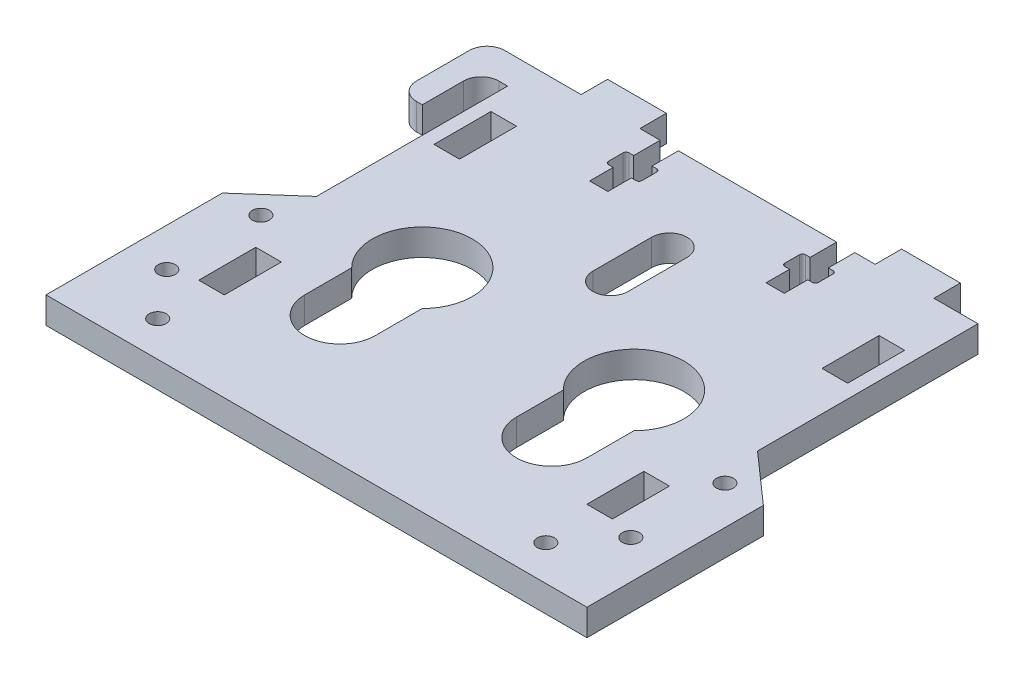
SolidWorks part; units mm, degrees
ref_plane "Front Plane" through (0, 0, 0) normal (0, 0, 1) x (1, 0, 0)
ref_plane "Top Plane" through (0, 0, 0) normal (0, 1, 0) x (1, 0, 0)
ref_plane "Right Plane" through (0, 0, 0) normal (1, 0, 0) x (0, 0, -1)
sketch "Sketch1" plane through (0, 0, 0) normal (0, 1, 0) x (1, 0, 0)
  line L1 (-37.5, 37.5) -> (37.5, 37.5)
  line L2 (-37.5, 37.5) -> (-37.5, -37.5)
  line L3 (-37.5, -37.5) -> (37.5, -37.5)
  line L4 (37.5, 37.5) -> (37.5, -37.5)
  line L5 (-37.5, 37.5) -> (37.5, -37.5) construction
  line L6 (-37.5, -37.5) -> (37.5, 37.5) construction
  point P0 (0, 0)
  dimension "D1" = 75
  dimension "D2" = 75
extrude "MainShape" add sketch "Sketch1" along normal blind 4.5
sketch "Sketch2" plane through (0, 4.5, 0) normal (0, 1, 0) x (1, 0, 0)
  line L0 (0, -37.5) -> (0, 37.5) construction
  line L1 (-37.5, -37.5) -> (37.5, -37.5) construction
  line L2 (37.5, 37.5) -> (-37.5, 37.5) construction
  line L4 (-5, 42) -> (5, 42)
  line L5 (-5, 42) -> (-5, 33)
  line L6 (-5, 33) -> (5, 33)
  line L7 (5, 42) -> (5, 33)
  line L8 (-5, 42) -> (5, 33) construction
  line L9 (-5, 33) -> (5, 42) construction
  dimension "D1" = 10
  dimension "D2" = 4.5
extrude "Tab1" [suppressed] add sketch "Sketch2" against normal through all
sketch "Sketch4" [suppressed] plane through (0, 4.5, 0) normal (0, 1, 0) x (1, 0, 0)
  line L0 (0, 42) -> (0, -37.5) construction
  line L1 (5, 42) -> (-5, 42) construction
  line L2 (-47.5, -37.5) -> (47.5, -37.5) construction
  line L3 (-40, 37.5) -> (-40, 27) construction
  line L4 (-5, 37.5) -> (-47.5, 37.5) construction
  line L5 (-38.25, 27) -> (-41.75, 27) construction
  line L6 (-41.75, 27) -> (-41.75, 37.5) construction
  line L7 (-38.25, 27) -> (-41.75, 27)
  line L8 (-41.75, 27) -> (-41.75, 29.5)
  line L9 (-41.75, 29.5) -> (-42.75, 29.5)
  line L10 (-43, 29.75) -> (-43, 33.45)
  line L11 (-42.75, 33.7) -> (-41.75, 33.7)
  line L12 (-41.75, 33.7) -> (-41.75, 37.5)
  line L13 (-41.75, 37.5) -> (-38.25, 37.5)
  line L14 (-38.25, 27) -> (-38.25, 37.5) construction
  line L15 (-38.25, 33.7) -> (-38.25, 37.5)
  line L16 (-37.25, 33.7) -> (-38.25, 33.7)
  line L17 (-37, 29.75) -> (-37, 33.45)
  line L18 (-38.25, 29.5) -> (-37.25, 29.5)
  line L19 (-38.25, 27) -> (-38.25, 29.5)
  line L20 (38.25, 27) -> (38.25, 37.5) construction
  line L21 (41.75, 27) -> (41.75, 37.5) construction
  line L22 (38.25, 27) -> (41.75, 27) construction
  line L23 (40, 37.5) -> (40, 27) construction
  line L24 (38.25, 27) -> (38.25, 29.5)
  line L25 (38.25, 29.5) -> (37.25, 29.5)
  line L26 (37, 29.75) -> (37, 33.45)
  line L27 (37.25, 33.7) -> (38.25, 33.7)
  line L28 (38.25, 33.7) -> (38.25, 37.5)
  line L29 (41.75, 37.5) -> (38.25, 37.5)
  line L30 (41.75, 33.7) -> (41.75, 37.5)
  line L31 (42.75, 33.7) -> (41.75, 33.7)
  line L32 (43, 29.75) -> (43, 33.45)
  line L33 (41.75, 29.5) -> (42.75, 29.5)
  line L34 (41.75, 27) -> (41.75, 29.5)
  line L35 (38.25, 27) -> (41.75, 27)
  arc A0 (-42.75, 29.5) -> (-43, 29.75) centre (-42.75, 29.75) cw
  arc A1 (-37, 29.75) -> (-37.25, 29.5) centre (-37.25, 29.75) cw
  arc A2 (-37.25, 33.7) -> (-37, 33.45) centre (-37.25, 33.45) cw
  arc A3 (-43, 33.45) -> (-42.75, 33.7) centre (-42.75, 33.45) cw
  arc A4 (43, 33.45) -> (42.75, 33.7) centre (42.75, 33.45) ccw
  arc A5 (37.25, 33.7) -> (37, 33.45) centre (37.25, 33.45) ccw
  arc A6 (37, 29.75) -> (37.25, 29.5) centre (37.25, 29.75) ccw
  arc A7 (42.75, 29.5) -> (43, 29.75) centre (42.75, 29.75) ccw
  point P24 (-43, 29.5)
  point P27 (-37, 29.5)
  point P30 (-37, 33.7)
  point P33 (-43, 33.7)
  point P56 (43, 33.7)
  point P57 (37, 33.7)
  point P58 (37, 29.5)
  point P59 (43, 29.5)
  dimension "D7" = 0.5
  dimension "D1" = 11
  dimension "D2" = 1.55
  dimension "D3" = 3.5
  dimension "D4" = 2.85
  dimension "D5" = 8
  dimension "D6" = 40
extrude "Cut-Extrude2" [suppressed] cut sketch "Sketch4" against normal through all
sketch "Sketch5" plane through (0, 4.5, 0) normal (0, 1, 0) x (1, 0, 0)
  line L0 (0, -37.5) -> (0, 37.5) construction
  line L1 (-37.5, -37.5) -> (37.5, -37.5) construction
  line L3 (33, 37.5) -> (33, -37.5) construction
  line L4 (37.5, 37.5) -> (-37.5, 37.5) construction
  line L5 (-33, 37.5) -> (-33, -37.5) construction
  line L6 (30.825, 27.35) -> (35.175, 27.35)
  line L7 (30.825, 27.35) -> (30.825, 17.65)
  line L8 (30.825, 17.65) -> (35.175, 17.65)
  line L9 (35.175, 27.35) -> (35.175, 17.65)
  line L10 (30.825, 27.35) -> (35.175, 17.65) construction
  line L11 (30.825, 17.65) -> (35.175, 27.35) construction
  line L12 (-30.825, 17.65) -> (-35.175, 27.35) construction
  line L13 (-30.825, 27.35) -> (-35.175, 17.65) construction
  line L14 (-35.175, 27.35) -> (-35.175, 17.65)
  line L15 (-30.825, 17.65) -> (-35.175, 17.65)
  line L16 (-30.825, 27.35) -> (-30.825, 17.65)
  line L17 (-30.825, 27.35) -> (-35.175, 27.35)
  line L18 (-37.5, 2.5) -> (37.5, 2.5) construction
  line L19 (-37.5, 37.5) -> (-37.5, -37.5) construction
  line L20 (37.5, -37.5) -> (37.5, 37.5) construction
  line L21 (-30.825, -22.35) -> (-35.175, -12.65) construction
  line L22 (-30.825, -12.65) -> (-35.175, -22.35) construction
  line L23 (30.825, -12.65) -> (35.175, -22.35) construction
  line L24 (30.825, -22.35) -> (35.175, -12.65) construction
  line L25 (-30.825, -22.35) -> (-35.175, -22.35)
  line L26 (-30.825, -22.35) -> (-30.825, -12.65)
  line L27 (-30.825, -12.65) -> (-35.175, -12.65)
  line L28 (-35.175, -22.35) -> (-35.175, -12.65)
  line L29 (35.175, -22.35) -> (35.175, -12.65)
  line L30 (30.825, -12.65) -> (35.175, -12.65)
  line L31 (30.825, -22.35) -> (30.825, -12.65)
  line L32 (30.825, -22.35) -> (35.175, -22.35)
  line L33 (-30.825, 27.35) -> (-35.175, 17.65) construction
  line L34 (-37.5, 37.5) -> (37.5, 37.5) construction
  line L35 (37.5, 37.5) -> (-37.5, 37.5) construction
  point P10 (33, 22.5)
  point P21 (-33, 22.5)
  point P36 (-33, -17.5)
  point P37 (33, -17.5)
  dimension "D1" = 33
  dimension "D2" = 9.7
  dimension "D3" = 4.35
  dimension "D4" = 15
  dimension "D5" = 40
extrude "Cut-Extrude3" cut sketch "Sketch5" against normal through all
sketch "Sketch6" plane through (0, 4.5, 0) normal (0, 1, 0) x (1, 0, 0)
  line L0 (-18, -37.5) -> (-18, 28) construction
  line L1 (-24, -15.5) -> (-24, -7.5208)
  line L3 (-37.5, -15.5) -> (37.5, -15.5) construction
  line L4 (-37.5, 37.5) -> (-37.5, -37.5) construction
  line L5 (37.5, -37.5) -> (37.5, 37.5) construction
  line L6 (37.5, 37.5) -> (-37.5, 37.5) construction
  line L7 (-37.5, -37.5) -> (37.5, -37.5) construction
  line L8 (-12, -15.5) -> (-12, -7.5208)
  line L9 (-37.5, 37.5) -> (37.5, 37.5) construction
  arc A0 (-24, -15.5) -> (-12, -15.5) centre (-18, -15.5) ccw
  arc A2 (-12, -7.5208) -> (-24, -7.5208) centre (-18, -1.5) ccw
  dimension "D1" = 12
  dimension "D6" = 8.5
  dimension "D2" = 53
  dimension "D3" = 0
  dimension "D5" = 0
  dimension "D7" = 14
  dimension "D4" = 18
extrude "Cut-Extrude4" cut sketch "Sketch6" against normal through all
sketch "Sketch13" plane through (0, 4.5, 0) normal (0, 1, 0) x (1, 0, 0)
  line L0 (-37.5, 0) -> (-46, -7.5)
  line L1 (-37.5, 37.5) -> (-37.5, -37.5) construction
  line L2 (-46, -7.5) -> (-46, -37.5)
  line L3 (-46, -37.5) -> (-37.5, -37.5)
  line L4 (-37.5, -37.5) -> (-37.5, 0)
  line L5 (0, 37.5) -> (0, -37.5) construction
  line L6 (37.5, 37.5) -> (-37.5, 37.5) construction
  line L7 (-37.5, -37.5) -> (37.5, -37.5) construction
  line L8 (37.5, -37.5) -> (37.5, 0)
  line L9 (46, -37.5) -> (37.5, -37.5)
  line L10 (46, -7.5) -> (46, -37.5)
  line L11 (37.5, 0) -> (46, -7.5)
  line L12 (-37.5, -37.5) -> (-37.5, 0)
  line M23 (37.5, -37.5) -> (37.5, 37.5)
  line M25 (-37.5, 37.5) -> (-37.5, -37.5)
  dimension "D1" = 46
  dimension "D2" = 30
extrude "Boss-Extrude2" add sketch "Sketch13" against normal through all contours L2 L3 L0 M25 | L11 L9 L10 M23 region at (-41.5926, 4.5, 20.5556) region at (41.5926, 4.5, 20.5556)
sketch "Sketch8" plane through (0, 4.5, 0) normal (0, 1, 0) x (1, 0, 0)
  line L0 (-18, -9.5) -> (-18, -21.5) construction
  line L1 (-18, -15.5) -> (-39.46, -15.5) construction
  line L2 (-39.46, -23.5) -> (-39.46, -7.5) construction
  line L3 (-18, -21.5) -> (-18, -9.5) construction
  circle A0 centre (-39.46, -7.5) radius 1.45
  circle A1 centre (-18, -15.5) radius 6 construction
  circle A2 centre (-39.46, -23.5) radius 1.45
  dimension "D3" = 2.9
  dimension "D1" = 0
  dimension "D2" = 8
  dimension "D4" = 21.46
extrude "Cut-Extrude6" cut sketch "Sketch8" against normal through all
mirror "Mirror1" about plane through (0, 0, 0) normal (1, 0, 0) of "Cut-Extrude6", "Cut-Extrude4"
sketch "Sketch11" plane through (0, 4.5, 0) normal (0, 1, 0) x (1, 0, 0)
  line L0 (0, 37.5) -> (0, -37.5) construction
  line L1 (37.5, 37.5) -> (-37.5, 37.5) construction
  line L2 (-46, -37.5) -> (46, -37.5) construction
  line L3 (-25, 42) -> (-25, 37.5) construction
  line L4 (-30, 37.5) -> (-20, 37.5)
  line L5 (-30, 37.5) -> (-30, 42)
  line L6 (-30, 42) -> (-20, 42)
  line L7 (-20, 37.5) -> (-20, 42)
  line L8 (25, 42) -> (25, 37.5) construction
  line L9 (20, 37.5) -> (20, 42)
  line L10 (30, 42) -> (20, 42)
  line L11 (30, 37.5) -> (30, 42)
  line L12 (30, 37.5) -> (20, 37.5)
  dimension "D1" = 10
  dimension "D2" = 4.5
  dimension "D3" = 25
extrude "RearTabs" add sketch "Sketch11" against normal through all
sketch "Sketch12" plane through (0, 4.5, 0) normal (0, 1, 0) x (1, 0, 0)
  line L0 (-15, 0) -> (-15, 37.5) construction
  line L1 (20, 37.5) -> (-20, 37.5) construction
  line L2 (-13.45, 37.5) -> (-16.55, 37.5)
  line L3 (-16.55, 37.5) -> (-16.55, 33)
  line L4 (-16.55, 33) -> (-17.35, 33)
  line L5 (-17.85, 32.5) -> (-17.85, 30)
  line L6 (-17.35, 29.5) -> (-16.55, 29.5)
  line L7 (-16.55, 29.5) -> (-16.55, 25.5)
  line L8 (-16.55, 25.5) -> (-13.45, 25.5)
  line L9 (-13.45, 29.5) -> (-13.45, 25.5)
  line L10 (-12.65, 29.5) -> (-13.45, 29.5)
  line L11 (-12.15, 32.5) -> (-12.15, 30)
  line L12 (-13.45, 33) -> (-12.65, 33)
  line L13 (-13.45, 37.5) -> (-13.45, 33)
  line L14 (0, 37.5) -> (0, 23.4067) construction
  line L15 (13.45, 37.5) -> (13.45, 33)
  line L16 (13.45, 33) -> (12.65, 33)
  line L17 (12.15, 32.5) -> (12.15, 30)
  line L18 (12.65, 29.5) -> (13.45, 29.5)
  line L19 (13.45, 29.5) -> (13.45, 25.5)
  line L20 (16.55, 25.5) -> (13.45, 25.5)
  line L21 (16.55, 29.5) -> (16.55, 25.5)
  line L22 (17.35, 29.5) -> (16.55, 29.5)
  line L23 (17.85, 32.5) -> (17.85, 30)
  line L24 (16.55, 33) -> (17.35, 33)
  line L25 (16.55, 37.5) -> (16.55, 33)
  line L26 (13.45, 37.5) -> (16.55, 37.5)
  arc A0 (-17.85, 30) -> (-17.35, 29.5) centre (-17.35, 30) ccw
  arc A1 (-17.35, 33) -> (-17.85, 32.5) centre (-17.35, 32.5) ccw
  arc A2 (-12.65, 33) -> (-12.15, 32.5) centre (-12.65, 32.5) cw
  arc A3 (-12.15, 30) -> (-12.65, 29.5) centre (-12.65, 30) cw
  arc A4 (12.15, 30) -> (12.65, 29.5) centre (12.65, 30) ccw
  arc A5 (12.65, 33) -> (12.15, 32.5) centre (12.65, 32.5) ccw
  arc A6 (17.35, 33) -> (17.85, 32.5) centre (17.35, 32.5) cw
  arc A7 (17.85, 30) -> (17.35, 29.5) centre (17.35, 30) cw
  point P14 (-17.85, 29.5)
  point P17 (-17.85, 33)
  point P25 (-15, 25.5)
  point P28 (-12.15, 33)
  point P29 (-12.15, 29.5)
  point P53 (12.15, 29.5)
  point P54 (12.15, 33)
  point P55 (15, 25.5)
  point P56 (17.85, 33)
  point P57 (17.85, 29.5)
  dimension "D5" = 8
  dimension "D1" = 12
  dimension "D6" = 0.5
  dimension "D2" = 3.5
  dimension "D3" = 2.85
  dimension "D4" = 1.55
  dimension "D7" = 15
extrude "FrontScrewSlot" cut sketch "Sketch12" against normal through all
sketch "Sketch14" plane through (0, 4.5, 0) normal (0, 1, 0) x (1, 0, 0)
  line L0 (-33, 27.35) -> (-33, -37.5) construction
  line L1 (-30.825, 27.35) -> (-35.175, 27.35) construction
  line L2 (-46, -37.5) -> (46, -37.5) construction
  line L3 (-30, 37.5) -> (-37.5, 37.5) construction
  line L4 (0, 0) -> (0, -37.5) construction
  line L5 (33, 27.35) -> (33, -37.5) construction
  line L6 (-33, 27.35) -> (-33, -37.5) construction
  circle A0 centre (-33, -31.5) radius 1.45
  circle A1 centre (33, -31.5) radius 1.45
  dimension "D2" = 2.9
  dimension "D1" = 69
extrude "BraceScrews" cut sketch "Sketch14" against normal through all
sketch "Sketch15" plane through (0, 4.5, 0) normal (0, 1, 0) x (1, 0, 0)
  line L0 (0, -37.5) -> (0, 27.5) construction
  line L1 (-46, -37.5) -> (46, -37.5) construction
  line L3 (16, 27.5) -> (-16, 27.5) construction
  line L4 (-16.55, 37.5) -> (-20, 37.5) construction
  line L5 (-18.175, 32.35) -> (-13.825, 32.35)
  line L6 (-18.175, 32.35) -> (-18.175, 22.65)
  line L7 (-18.175, 22.65) -> (-13.825, 22.65)
  line L8 (-13.825, 32.35) -> (-13.825, 22.65)
  line L9 (-18.175, 32.35) -> (-13.825, 22.65) construction
  line L10 (-18.175, 22.65) -> (-13.825, 32.35) construction
  line L11 (18.175, 22.65) -> (13.825, 32.35) construction
  line L12 (18.175, 32.35) -> (13.825, 22.65) construction
  line L13 (13.825, 32.35) -> (13.825, 22.65)
  line L14 (18.175, 22.65) -> (13.825, 22.65)
  line L15 (18.175, 32.35) -> (18.175, 22.65)
  line L16 (18.175, 32.35) -> (13.825, 32.35)
  point P19 (0, 27.5)
  dimension "D1" = 16
  dimension "D2" = 4.35
  dimension "D3" = 9.7
  dimension "D4" = 10
extrude "FanTabs" [suppressed] cut sketch "Sketch15" against normal through all
sketch "Sketch16" plane through (0, 4.5, 0) normal (0, 1, 0) x (1, 0, 0)
  line L0 (0, 0) -> (0, 37.5) construction
  line L2 (0, 22.5) -> (0, 12.5) construction
  line L3 (3, 22.5) -> (3, 12.5)
  line L4 (-3, 22.5) -> (-3, 12.5)
  line L5 (13.45, 37.5) -> (-13.45, 37.5) construction
  arc A0 (3, 22.5) -> (-3, 22.5) centre (0, 22.5) ccw
  arc A1 (-3, 12.5) -> (3, 12.5) centre (0, 12.5) ccw
  point P7 (0, 17.5)
  dimension "D1" = 3
  dimension "D2" = 22.5
  dimension "D3" = 10
extrude "WiringSlot" cut sketch "Sketch16" against normal through all
sketch "Sketch17" [suppressed] plane through (0, 4.5, 0) normal (0, 1, 0) x (1, 0, 0)
  line L0 (-37.5, 14.5) -> (-37.5, 10.5) construction
  line L3 (-37.5, 37.5) -> (-37.5, 0) construction
  line L4 (-36, 14.5) -> (-36, 10.5)
  line L5 (-39, 14.5) -> (-39, 10.5)
  line L6 (-37.5, 14.5) -> (-37.5, 10.5) construction
  line L7 (-34, 14.5) -> (-34, 10.5)
  line L8 (-41, 14.5) -> (-41, 10.5)
  line L9 (-41, 12.5) -> (-37.5, 12.5) construction
  line L10 (0, 0) -> (0, -12.1805) construction
  arc A0 (-36, 14.5) -> (-39, 14.5) centre (-37.5, 14.5) ccw
  arc A1 (-39, 10.5) -> (-36, 10.5) centre (-37.5, 10.5) ccw
  arc A2 (-34, 14.5) -> (-41, 14.5) centre (-37.5, 14.5) ccw
  arc A3 (-41, 10.5) -> (-34, 10.5) centre (-37.5, 10.5) ccw
  point P4 (-37.5, 12.5)
  point P10 (-37.5, 12.5)
  dimension "D4" = 4
  dimension "D5" = 25
  dimension "D1" = 0
  dimension "D2" = 2
  dimension "D3" = 1.5
extrude "Boss-Extrude3" [suppressed] add sketch "Sketch17" against normal through all
mirror "Mirror2" [suppressed] about plane through (0, 0, 0) normal (1, 0, 0)
sketch "Sketch18" [suppressed] plane through (0, 4.5, 0) normal (0, 1, 0) x (1, 0, 0)
  line L0 (0, -37.5) -> (0, 47.6111) construction
  line L1 (-45, -37.5) -> (45, -37.5) construction
  line L2 (-12, 2) -> (-12, -19.46) construction
  line L3 (-4, -19.46) -> (-20, -19.46) construction
  circle A0 centre (-12, 2) radius 5
  circle A1 centre (-20, -19.46) radius 1.45
  circle A2 centre (-4, -19.46) radius 1.45
  dimension "D2" = 8
  dimension "D4" = 21.46
  dimension "D1" = 2.9
  dimension "D3" = 10
  dimension "D5" = 12
  dimension "D6" = 2
extrude "Cut-Extrude7" [suppressed] cut sketch "Sketch18" against normal through all
mirror "Mirror3" [suppressed] about plane through (0, 0, 0) normal (1, 0, 0)
sketch "Sketch19" [suppressed] plane through (0, 4.5, 0) normal (0, 1, 0) x (1, 0, 0)
  line L0 (-17, 2) -> (-7, 2) construction
  line L1 (-12, 2) -> (-4, 2) construction
  line L2 (-12, 4) -> (-4, 4)
  line L3 (-12, 0) -> (-4, 0)
  line L4 (-12, 7) -> (-12, -3) construction
  line L5 (0, 0) -> (0, 6.8806) construction
  line L6 (12, 7) -> (12, -3) construction
  line L7 (17, 2) -> (7, 2) construction
  line L8 (12, 2) -> (4, 2) construction
  line L9 (12, 4) -> (4, 4)
  line L10 (12, 0) -> (4, 0)
  circle A0 centre (-12, 2) radius 5 construction
  arc A1 (-12, 4) -> (-12, 0) centre (-12, 2) ccw
  arc A2 (-4, 0) -> (-4, 4) centre (-4, 2) ccw
  arc A3 (12, 4) -> (12, 0) centre (12, 2) cw
  arc A4 (4, 0) -> (4, 4) centre (4, 2) cw
  point P6 (-8, 2)
  point P23 (8, 2)
  dimension "D1" = 2
  dimension "D2" = 8
extrude "Cut-Extrude8" [suppressed] cut sketch "Sketch19" against normal through all
sketch "Sketch20" plane through (0, 4.5, 0) normal (0, 1, 0) x (1, 0, 0)
  line L0 (0, 0) -> (0, -37.5) construction
  line L1 (-46, -37.5) -> (46, -37.5) construction
  line L2 (-26.9758, -32.9017) -> (-26.9758, -26.6196)
  line L3 (-26.9758, -26.6196) -> (-6.5592, -26.6196)
  line L4 (-6.5592, -26.6196) -> (-6.5592, 9.4097)
  line L5 (-6.5592, 9.4097) -> (6.5592, 9.4097)
  line L6 (-26.9758, -32.9017) -> (26.9758, -32.9017)
  line L7 (6.5592, -26.6196) -> (6.5592, 9.4097)
  line L8 (26.9758, -26.6196) -> (6.5592, -26.6196)
  line L9 (26.9758, -32.9017) -> (26.9758, -26.6196)
  point P12 (0, -32.9017)
  point P13 (0, 9.4097)
extrude "Cut-Extrude9" [suppressed] cut sketch "Sketch20" against normal through all
sketch "Sketch21" plane through (0, 4.5, 0) normal (0, 1, 0) x (1, 0, 0)
  line L0 (-46, -37.5) -> (-46, 37.5) construction
  line L1 (-37, 37.5) -> (-43, 37.5)
  line L4 (-46, 34.5) -> (-46, 25.5)
  line L5 (-43, 22.5) -> (-42, 22.5)
  line L6 (-42, 22.5) -> (-42, 29.5)
  line L7 (-39, 32.5) -> (-37, 32.5)
  line L9 (-37, 32.5) -> (-37, 37.5)
  line L10 (-30, 37.5) -> (-37.5, 37.5) construction
  line L11 (-37.5, 37.5) -> (-37.5, 0) construction
  arc A0 (-42, 29.5) -> (-39, 32.5) centre (-39, 29.5) cw
  arc A1 (-46, 25.5) -> (-43, 22.5) centre (-43, 25.5) ccw
  arc A2 (-43, 37.5) -> (-46, 34.5) centre (-43, 34.5) ccw
  point P19 (-46, 22.5)
  point P24 (-42, 37.5)
  dimension "D1" = 3
  dimension "D4" = 3
  dimension "D2" = 15
  dimension "D3" = 5
  dimension "D5" = 4
  dimension "D6" = 0.5
  dimension "D7" = 0
extrude "Boss-Extrude4" add sketch "Sketch21" against normal through all
sketch "Sketch22" plane through (0, 4.5, 0) normal (0, 1, 0) x (1, 0, 0)
  line L0 (-46, -7.5) -> (-46, 13.5)
  line L1 (-43, 16.5) -> (-42, 16.5)
  line L2 (-42, 16.5) -> (-42, -3.9706)
  line L3 (-37.5, 0) -> (-46, -7.5) construction
  line L4 (-42, -3.9706) -> (-46, -7.5)
  line L5 (-46, 16.5) -> (-46, 28.3122) construction
  line L6 (-46, 34.5) -> (-46, 25.5) construction
  line L7 (-42, 22.6875) -> (-42, 12.0504) construction
  line L8 (-42, 22.5) -> (-42, 29.5) construction
  arc A0 (-46, 13.5) -> (-43, 16.5) centre (-43, 13.5) cw
  dimension "D2" = 3
  dimension "D1" = 6
extrude "Boss-Extrude5" [suppressed] add sketch "Sketch22" against normal through all
mirror "Mirror6" [suppressed] about plane through (0, 0, 0) normal (1, 0, 0)
equation "\"X-ROD-SPACING\"=45"
equation "\"Y-ROD-SPACING\"=75"
equation "\"Z-ROD-SPACING\"=17.5"
equation "\"Y-BED-OFFSET\"=2"
equation "\"Y-BED-ROD-INSET\"=3.5"
equation "\"Y-BED-SCREW-SPACING\"=209"
equation "\"Y-BED-SCREW-CUTOUT-SLOT-HEIGHT\"=2.5"
equation "\"T-SLOT-NUT-FILLET-RADIUS\"=0.5"
equation "\"T-SLOT-SCREW-SHAFT-RADIUS\"=1.55"
equation "\"T-SLOT-SCREW-SHAFT-CUTOUT-LENGTH\"=11"
equation "\"T-SLOT-NUT-DEPTH\"=3.5"
equation "\"T-SLOT-NUT-WIDTH\"=2.85"
equation "\"T-SLOT-NUT-END-DISTANCE\"=8"
equation "\"ACRYLIC-THICKNESS\"=10"
equation "\"ACRYLIC-THICKNESS2\"=4.5"
equation "\"ACRYLIC-TAB-CUTOUT-SIZE\"=\"ACRYLIC-THICKNESS\"+\"ACRYLIC-TAB-TOLERANCE\"*2"
equation "\"ACRYLIC-TAB-WIDTH\"=\"ACRYLIC-THICKNESS\""
equation "\"ACRYLIC-M3-HOLE\"=2.9"
equation "\"SMOOTHROD-CAP-SCREW-DISTANCE\"=20"
equation "\"FRAME-WIDTH-INNER\"=370"
equation "\"NEMA17-HOLE-SPACING\"=31"
equation "\"NEMA17-CENTRAL-CUTOUT\"=22.5"
equation "\"Z-BRACKET-REACH\"=57"
equation "\"Z-ROD-INSET\"=13.5"
equation "\"TOP-BRACKET-SPACING\"=40"
equation "\"SMOOTHROD-X-LENGTH\"=350"
equation "\"SMOOTHROD-Y-LENGTH\"=350"
equation "\"SMOOTHROD-Z-LENGTH\"=350"
equation "\"SMOOTHROD-TIGHTENING-HEADROOM\"=.25"
equation "\"LEADSCREW-Z-LENGTH\"=300"
equation "\"SCREW-LENGTH-FRAME\"=\"ACRYLIC-THICKNESS\" + 10"
equation "\"SCREW-LENGTH-MOTOR\"=\"ACRYLIC-THICKNESS\" + 5"
equation "\"SCREW-LENGTH-EXTRUDER\"=28"
equation "\"SCREW-HEAD-RADIUS\"=6"
equation "\"PRINTED-X-SMOOTHROD-DIAMETER\"=8.8"
equation "\"PRINTED-X-SMOOTHROD-CUTOUT\"=10"
equation "\"PRINTED-X-BASE-HEIGHT\"=10"
equation "\"PRINTED-LM8UU-CUTOUT-SIZE\"=15.5"
equation "\"PRINTED-LM8UU-CUTOUT-LENGTH\"=24.5"
equation "\"PRINTED-X-IDLER-HEIGHT\"=16"
equation "\"PSU-MOUNTING-WIDTH\"=95"
equation "\"PSU-MOUNTING-HEIGHT\"=177"
equation "\"Y-BELT-TO-ROD-DISTANCE\"=20"
equation "\"SPOOL-HOLDER-ROD-SPACING\"=150"
equation "\"ACRYLIC-X-CARRIAGE-WIDTH\"=55"
equation "\"ACRYLIC-X-CARRIAGE-HEIGHT\"=75"
equation "\"ACRYLIC-X-CARRIAGE-SCREW-SPACING-X\"=15"
equation "\"ACRYLIC-X-CARRIAGE-SCREW-SPACING-Y\"=33"
equation "\"ACRYLIC-X-CARRIAGE-CENTER-TAB-SPACING\"=14"
equation "\"D1@MainShape\" = \"ACRYLIC-THICKNESS2\""
equation "\"D1@Sketch2\"=\"ACRYLIC-TAB-WIDTH\""
equation "\"D2@Sketch2\"=\"ACRYLIC-THICKNESS2\""
equation "\"D1@Sketch4\"=\"T-SLOT-SCREW-SHAFT-CUTOUT-LENGTH\""
equation "\"D2@Sketch4\"=\"T-SLOT-SCREW-SHAFT-RADIUS\""
equation "\"D3@Sketch4\"=\"T-SLOT-NUT-DEPTH\""
equation "\"D4@Sketch4\"=\"T-SLOT-NUT-WIDTH\""
equation "\"D5@Sketch4\"=\"T-SLOT-NUT-END-DISTANCE\""
equation "\"D7@Sketch4\"=\"T-SLOT-NUT-FILLET-RADIUS\""
equation "\"ACRYLIC-X-CARRIAGE-EXTRUDER-SHELF-DEPTH\"=\"ACRYLIC-X-CARRIAGE-EXTRUDER-OFFSET\" + 28"
equation "\"ACRYLIC-X-CARRIAGE-LM8UU-CUTOUT-WIDTH\"=24.25"
equation "\"ACRYLIC-X-CARRIAGE-EXTRUDER-BRACE-SPACING\"=23"
equation "\"ACRYLIC-X-CARRIAGE-EXTRUDER-BRACE-TAB-OFFSET\"=20"
equation "\"ACRYLIC-X-CARRIAGE-EXTRUDER-BRACE-HEIGHT\"=35"
equation "\"ACRYLIC-X-CARRIAGE-EXTRUDER-BRACE-SCREW-SPACING\"=22"
equation "\"D2@Sketch5\"=\"ACRYLIC-THICKNESS2-TAB-CUTOUT-HEIGHT\""
equation "\"D3@Sketch5\"=\"ACRYLIC-THICKNESS2-TAB-CUTOUT-WIDTH\""
equation "\"D3@Sketch8\"=\"ACRYLIC-M3-HOLE\""
equation "\"ACRYLIC-X-CARRIAGE-EXTRUDER-ANGLE\"=90"
equation "\"ACRYLIC-X-CARRIAGE-EXTRUDER-OFFSET\"=26"
equation "\"ACRYLIC-TAB-TOLERANCE\"=-.05"
equation "\"ACRYLIC-X-CARRIAGE-DUAL-WIDTH-MULTIPLIER\"=1.65"
equation "\"ACRYLIC-X-CARRIAGE-DUAL-HOTEND-SPACING\"=42"
equation "\"ACRYLIC-X-CARRIAGE-DUAL-WIDTH\"=75"
equation "\"ACRYLIC-X-CARRIAGE-DUAL-HOTEND-SEPARATION\"=36"
equation "\"ACRYLIC-X-CARRIAGE-DUAL-MOUNT-PLATE-DEPTH\"=75"
equation "\"ACRYLIC-X-CARRIAGE-DUAL-MOUNT-BRACE-WIDTH\"=33"
equation "\"D1@Sketch5\"=\"ACRYLIC-X-CARRIAGE-DUAL-MOUNT-BRACE-WIDTH\""
equation "\"ACRYLIC-X-CARRIAGE-DUAL-MOUNT-SCREW-WIDTH\"=40"
equation "\"D6@Sketch4\"=\"ACRYLIC-X-CARRIAGE-DUAL-MOUNT-SCREW-WIDTH\""
equation "\"D1@Sketch1\"=\"ACRYLIC-X-CARRIAGE-DUAL-WIDTH\""
equation "\"D2@Sketch1\"=\"ACRYLIC-X-CARRIAGE-DUAL-MOUNT-PLATE-DEPTH\""
equation "\"D4@Sketch6\"=\"ACRYLIC-X-CARRIAGE-DUAL-HOTEND-SEPARATION\"/2"
equation "\"D1@Sketch11\"=\"ACRYLIC-TAB-WIDTH\""
equation "\"D2@Sketch11\"=\"ACRYLIC-THICKNESS2\""
equation "\"D1@Sketch12\"=\"T-SLOT-SCREW-SHAFT-CUTOUT-LENGTH\"+1"
equation "\"D2@Sketch12\"=\"T-SLOT-NUT-DEPTH\""
equation "\"D3@Sketch12\"=\"T-SLOT-NUT-WIDTH\""
equation "\"D4@Sketch12\"=\"T-SLOT-SCREW-SHAFT-RADIUS\""
equation "\"D5@Sketch12\"=\"T-SLOT-NUT-END-DISTANCE\""
equation "\"D6@Sketch12\"=\"T-SLOT-NUT-FILLET-RADIUS\""
equation "\"D2@Sketch14\"=\"ACRYLIC-M3-HOLE\""
equation "\"D2@Sketch15\"=\"ACRYLIC-THICKNESS2-TAB-CUTOUT-WIDTH\""
equation "\"D3@Sketch15\"=\"ACRYLIC-THICKNESS2-TAB-CUTOUT-HEIGHT\""
equation "\"KERF\"=0.075"
equation "\"PRINTED-M3-HOLE\"=3.5"
equation "\"PRINTED-M3-NUT-AF\"=6.25"
equation "\"ACRYLIC-X-CARRIAGE-LM8UU-CUTOUT-HEIGHT\"=11.0"
equation "\"ACRYLIC-X-CARRIAGE-DUAL-FAN-OFFSET\"=52"
equation "\"ACRYLIC-X-CARRIAGE-DUAL-FAN-HEIGHT\"=20"
equation "\"BLOWER-FAN-WIDTH\"=15"
equation "\"ACRYLIC-THICKNESS-TAB-CUTOUT-WIDTH\"=\"ACRYLIC-THICKNESS\"-\"KERF\"*2"
equation "\"ACRYLIC-THICKNESS-TAB-CUTOUT-HEIGHT\"=\"ACRYLIC-TAB-WIDTH\"-\"KERF\"*4"
equation "\"ACRYLIC-THICKNESS2-TAB-CUTOUT-WIDTH\"=\"ACRYLIC-THICKNESS2\"-\"KERF\"*2"
equation "\"ACRYLIC-THICKNESS2-TAB-CUTOUT-HEIGHT\"=\"ACRYLIC-TAB-WIDTH\"-\"KERF\"*4"
equation "\"D1@Sketch18\"=\"ACRYLIC-M3-HOLE\""
equation "\"D7@Sketch12\"=\"ACRYLIC-X-CARRIAGE-SCREW-SPACING-X\""
